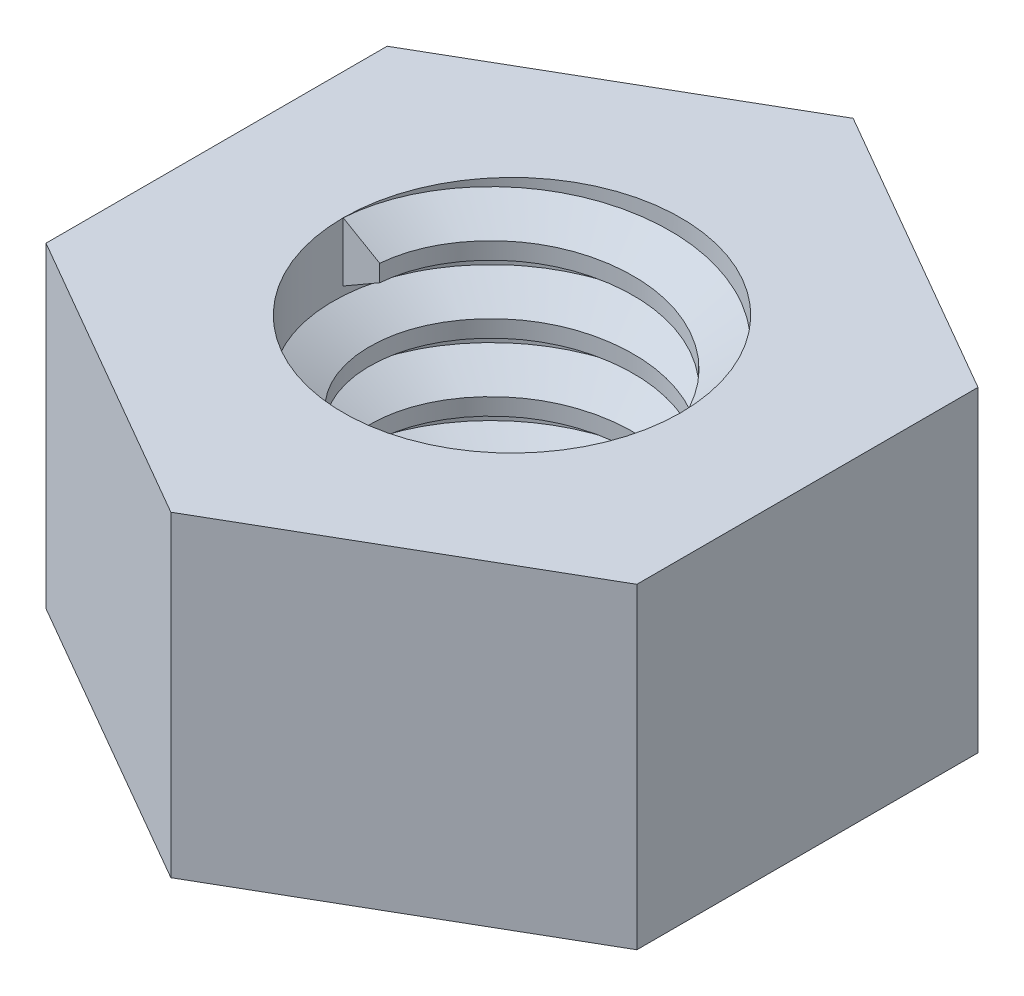
SolidWorks part; units mm, degrees
material "Nylon 6/10"
ref_plane "Front Plane" through (0, 0, 0) normal (0, 0, 1) x (1, 0, 0)
ref_plane "Top Plane" through (0, 0, 0) normal (0, 1, 0) x (1, 0, 0)
ref_plane "Right Plane" through (0, 0, 0) normal (1, 0, 0) x (0, 0, -1)
sketch "Sketch1" plane through (0, 0, 0) normal (0, 1, 0) x (1, 0, 0)
  line L1 (0, 6.4158) -> (-5.5562, 3.2079)
  line L2 (-5.5562, 3.2079) -> (-5.5562, -3.2079)
  line L3 (-5.5562, -3.2079) -> (0, -6.4158)
  line L4 (0, -6.4158) -> (5.5562, -3.2079)
  line L5 (5.5562, -3.2079) -> (5.5562, 3.2079)
  line L6 (5.5562, 3.2079) -> (0, 6.4158)
  circle A0 centre (0, 0) radius 3.175
  circle A1 centre (0, 0) radius 5.5562 construction
  dimension "D1" = 6.35
  dimension "D2" = 11.1125
extrude "Boss-Extrude1" add sketch "Sketch1" along normal blind 5.9531
thread "Thread1" pitch 1.27 method extrude profile "Thread Profile1" start angle 0, offset 0, length 0, pitch 1.27, diameter 6.35
ref_plane "Plane1" through (-3.175, 5.9531, 0) normal (0, 0, 1) x (-1, 0, 0)
sketch "Thread Profile1" plane through (-3.175, 5.9531, 0) normal (0, 0, 1) x (-1, 0, 0)
  line L0 (0, 0) -> (0, 1.27) construction
  line L11 (0, 0) -> (0, 1.1112)
  line L12 (0, 1.1112) -> (-0.6874, 0.7144)
  line L13 (-0.6874, 0.7144) -> (-0.6874, 0.3969)
  line L15 (-0.6874, 0.3969) -> (0, 0)
  line L17 (-0.6874, 0.5556) -> (0, 0.5556) construction
  point P2 (0, 0)
  dimension "Pitch" = 1.27
  dimension "Profile_Angle" = 60
  dimension "Profile_Land" = 0.3175
  dimension "Profile_Height" = 0.6874
